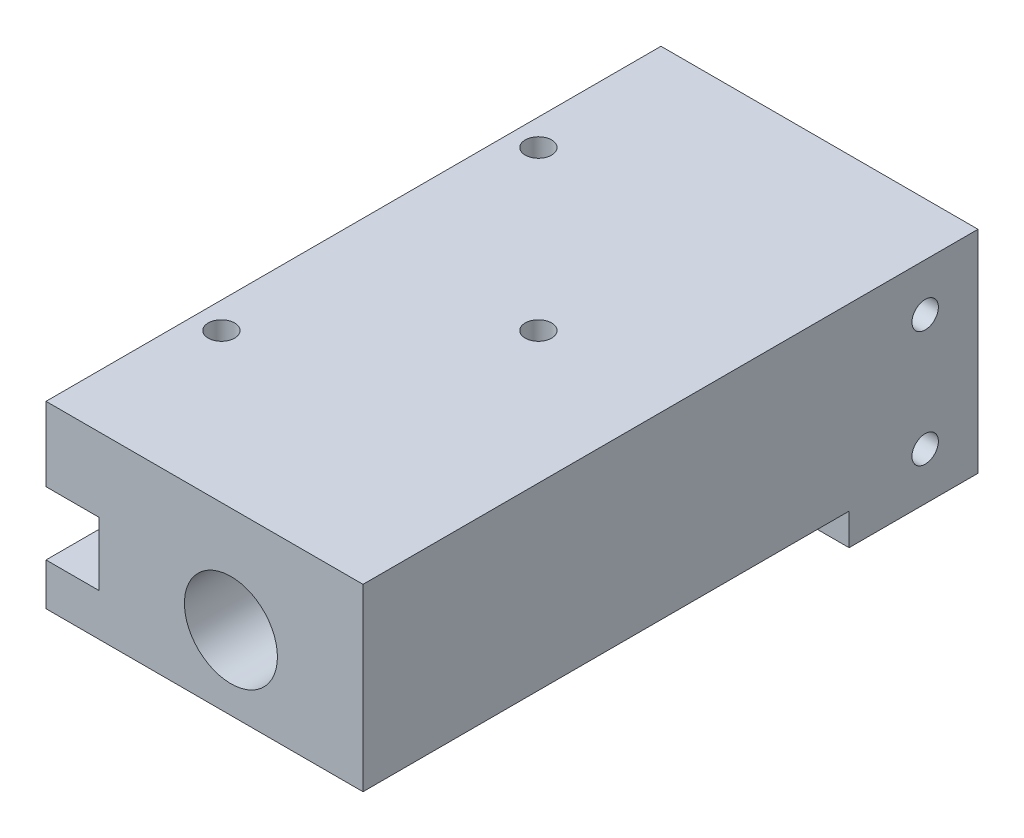
SolidWorks part; units mm, degrees
material "6063-T5"
ref_plane "Piano frontale" through (0, 0, 0) normal (0, 0, 1) x (1, 0, 0)
ref_plane "Piano superiore" through (0, 0, 0) normal (0, 1, 0) x (1, 0, 0)
ref_plane "Piano destro" through (0, 0, 0) normal (1, 0, 0) x (0, 0, -1)
sketch "Schizzo1" plane through (0, 0, 0) normal (0, 0, 1) x (1, 0, 0)
  line L1 (12.5, -10) -> (-12.5, -10)
  line L2 (12.5, -10) -> (12.5, 10)
  line L3 (12.5, 10) -> (-12.5, 10)
  line L4 (-12.5, -10) -> (-12.5, 10)
  line L5 (12.5, -10) -> (-12.5, 10) construction
  line L6 (12.5, 10) -> (-12.5, -10) construction
  point P0 (0, 0)
  dimension "D1" = 20
  dimension "D2" = 25
extrude "Estrusione-Estrusione1" add sketch "Schizzo1" against normal blind 58.2
sketch "Schizzo2" plane through (0, 0, -58.2) normal (0, 0, -1) x (-1, 0, 0)
  circle A0 centre (0, 0) radius 3
  dimension "D1" = 6
extrude "Taglio-Estrusione1" cut sketch "Schizzo2" against normal through all
sketch "Schizzo3" plane through (0, 0, -58.2) normal (0, 0, -1) x (-1, 0, 0)
  point P0 (0, 0)
hole_wizard "Foro filettato G1/8-1" positions "Schizzo8" profile "Schizzo7" tap size "G1/8" standard "BSI"
sketch "Schizzo8" plane through (0, 0, 0) normal (0, 0, 1) x (1, 0, 0)
  point P0 (0, 0)
sketch "Schizzo7" plane through (0, 0, 0) normal (1, 0, 0) x (0, -1, 0)
  line L0 (0, 0) -> (0, 12.6438)
  line L1 (0, 12.6438) -> (4.4, 10)
  line L2 (4.4, 10) -> (4.4, 0)
  line L5 (4.4, 0) -> (0, 0)
  line L10 (0, 12.6438) -> (-4.4, 10) construction
  line L11 (0, -6.35) -> (0, 107.95) construction
  dimension "Tap Drill Dia." = 8.8
  dimension "Tap Drill Depth" = 10
  dimension "Drill Angle" = 118
sketch "Schizzo10" plane through (12.5, 0, 0) normal (1, 0, 0) x (0, 0, -1)
  line L0 (0, -7) -> (46, -7)
  line L1 (0, -10) -> (0, 10) construction
  line L2 (46, -7) -> (46, -10)
  line L3 (58.2, -10) -> (0, -10) construction
  dimension "D1" = 46
  dimension "D2" = 3
extrude "Taglio-Estrusione5" cut sketch "Schizzo10" against normal through all and the other way through all flip side to cut
sketch "Schizzo11" plane through (0, 10, 0) normal (0, 1, 0) x (1, 0, 0)
  line L0 (0, 58.2) -> (0, 0) construction
  line L1 (12.5, 58.2) -> (-12.5, 58.2) construction
  line L2 (12.5, 29.1) -> (-17.5, 29.1) construction
  line L3 (12.5, 58.2) -> (12.5, 0) construction
  point P10 (0, 29.1)
  point P11 (0, 29.1)
  point P12 (0, 29.1)
hole_wizard "M3 Tapped Hole2" positions "Schizzo3D1" profile "Schizzo12" tap size "M3" standard "DIN"
sketch3d "Schizzo3D1"
  point P0 (0, 10, -29.1)
sketch "Schizzo12" plane through (0, 10, -29.1) normal (1, 0, 0) x (0, 0, 1)
  line L0 (0, 0) -> (0, 5.7511)
  line L1 (0, 5.7511) -> (1.25, 5)
  line L2 (1.25, 5) -> (1.25, 0)
  line L5 (1.25, 0) -> (0, 0)
  line L10 (0, 5.7511) -> (-1.25, 5) construction
  line L11 (0, -6.35) -> (0, 107.95) construction
  dimension "Tap Drill Dia." = 2.5
  dimension "Tap Drill Depth" = 5
  dimension "Drill Angle" = 118
cosmetic thread "Hole Thread4" parameters "D1"=5, "D2"=3
hole_wizard "Foro Ø16.0 (16)-1" positions "Schizzo3D3" profile "Schizzo14" hole size "Ø16.0" standard "ISO"
sketch3d "Schizzo3D3"
  point P0 (0, 0, 0)
  point P3 (0, 0, -58.2)
sketch "Schizzo14" plane through (0, 0, -58.2) normal (1, 0, 0) x (0, 1, 0)
  line L0 (0, 0) -> (0, 16.8069)
  line L1 (0, 16.8069) -> (8, 12)
  line L2 (8, 12) -> (8, 0)
  line L5 (8, 0) -> (0, 0)
  line L10 (0, 16.8069) -> (-8, 12) construction
  line L11 (0, -6.35) -> (0, 107.95) construction
  dimension "Hole Dia." = 16
  dimension "Hole Depth" = 12
  dimension "Drill Angle" = 118
sketch "Schizzo15" plane through (12.5, 0, 0) normal (1, 0, 0) x (0, 0, -1)
  line L0 (46.2, 0) -> (58.2, 0) construction
  line L1 (46.2, 8) -> (46.2, -8) construction
  line L4 (58.2, -10) -> (58.2, 10) construction
  line L6 (58.2, -10) -> (46, -10) construction
  point P5 (53.2, -5.5)
  point P8 (53.2, 5.5)
  dimension "D1" = 5.5
  dimension "D2" = 7
  dimension "D3" = 5
  dimension "D4" = 4.5
hole_wizard "Foro filettato M3-2" positions "Schizzo3D4" profile "Schizzo16" tap size "M3" standard "ISO" end condition through all
sketch3d "Schizzo3D4"
  point P0 (12.5, 5.5, -53.2)
  point P3 (12.5, -5.5, -53.2)
sketch "Schizzo16" plane through (12.5, 5.5, -53.2) normal (0, 1, 0) x (0, 0, -1)
  line L0 (0, 0) -> (0, 25)
  line L1 (0, 25) -> (1.25, 25)
  line L2 (1.25, 25) -> (1.25, 0)
  line L5 (1.25, 0) -> (0, 0)
  line L11 (0, -6.35) -> (0, 107.95) construction
  dimension "Thread Major Dia." = 2.5
  dimension "Thru Tap Drill Depth" = 25
sketch "Sketch5" plane through (-12.5, 0, 0) normal (-1, 0, 0) x (0, 0, 1)
  line L0 (-58.2, 3) -> (0, 3)
  line L1 (-58.2, 10) -> (-58.2, -10) construction
  line L2 (0, 10) -> (0, -7) construction
  line L3 (0, 10) -> (-58.2, 10)
  line L4 (-58.2, 10) -> (-58.2, 3)
  line L5 (-58.2, -10) -> (-58.2, -3)
  line L6 (-58.2, -3) -> (0, -3)
  line L7 (0, -3) -> (0, -7)
  line L8 (0, -7) -> (-46, -7)
  line L9 (-46, -7) -> (-46, -10)
  line L10 (-46, -10) -> (-58.2, -10)
  line L11 (0, 10) -> (0, 3)
  dimension "D1" = 6
  dimension "D2" = 7
extrude "Boss-Extrude2" add sketch "Sketch5" along normal blind 5
sketch "Sketch6" plane through (0, 10, 0) normal (0, 1, 0) x (1, 0, 0)
  line L0 (-17.5, 29.1) -> (12.5, 29.1) construction
  line L1 (-17.5, 0) -> (-17.5, 58.2) construction
  point P0 (-15, 44.1)
  point P5 (-15, 14.1)
  dimension "D1" = 15
  dimension "D2" = 2.5
hole_wizard "M3 Tapped Hole1" positions "3DSketch4" profile "Sketch10" tap size "M3" standard "ISO" end condition up to next
sketch3d "3DSketch4"
  point P0 (-15, 10, -44.1)
  point P3 (-84.0335, 0, -45.0925)
  point P5 (-15, 10, -14.1)
sketch "Sketch10" plane through (-15, 10, -44.1) normal (1, 0, 0) x (0, 0, 1)
  line L0 (0, 0) -> (0, 7)
  line L1 (0, 7) -> (1.25, 7)
  line L2 (1.25, 7) -> (1.25, 0)
  line L5 (1.25, 0) -> (0, 0)
  line L11 (0, -6.35) -> (0, 107.95) construction
  dimension "Thru Tap Drill Dia." = 2.5
  dimension "Thru Tap Drill Depth" = 7
cosmetic thread "Hole Thread1" parameters "D2"=3
cosmetic thread "Hole Thread2" parameters "D2"=3
cosmetic thread "Hole Thread3" parameters "D2"=3
